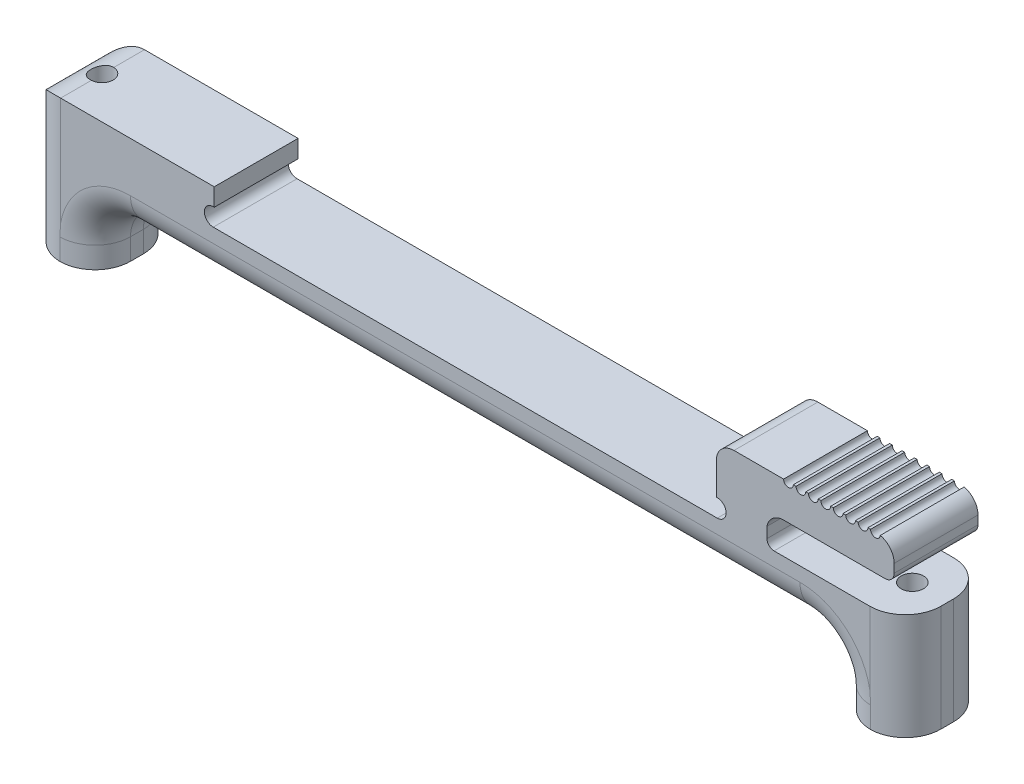
SolidWorks part; units mm, degrees
material "ABS"
ref_plane "Front" through (0, 0, 0) normal (0, 0, 1) x (1, 0, 0)
ref_plane "Top" through (0, 0, 0) normal (0, 1, 0) x (1, 0, 0)
ref_plane "Right" through (0, 0, 0) normal (1, 0, 0) x (0, 0, -1)
ref_axis "Axis1" through (0, 0, 55) along (0, 0, -1)
sketch "Sketch1" plane through (0, 0, 0) normal (0, 0, 1) x (1, 0, 0)
  line L0 (-28.9941, 0) -> (28.9941, 0) construction
  line L1 (-31.4941, 0) -> (-26.4941, 0)
  line L2 (-26.4941, 0) -> (-26.4941, 1.524)
  line L3 (-23.9541, 4.064) -> (23.9541, 4.064)
  line L4 (26.4941, 1.524) -> (26.4941, 0)
  line L5 (26.4941, 0) -> (31.4941, 0)
  line L6 (-31.4941, 0) -> (-31.4941, 10.1561)
  line L7 (-31.4941, 10.1561) -> (-17.9634, 10.1561)
  line L8 (-17.9634, 10.1561) -> (-17.9634, 8.8861)
  line L9 (-18.034, 7.62) -> (18.034, 7.62)
  line L10 (0, 0) -> (0, 15.2653) construction
  line L11 (31.4941, 0) -> (31.4941, 10.1561)
  line L12 (31.4941, 10.1561) -> (17.9634, 10.1561)
  line L13 (17.9634, 10.1561) -> (17.9634, 8.8861)
  arc A0 (-17.9634, 8.8861) -> (-18.034, 7.62) centre (-18.034, 8.255) ccw
  arc A1 (17.9634, 8.8861) -> (18.034, 7.62) centre (18.034, 8.255) cw
  arc A2 (26.4941, 1.524) -> (23.9541, 4.064) centre (23.9541, 1.524) ccw
  arc A3 (-23.9541, 4.064) -> (-26.4941, 1.524) centre (-23.9541, 1.524) ccw
  point P4 (0, 0)
  point P8 (-28.9941, 0)
  point P20 (0, 7.62)
  point P26 (28.9941, 0)
  dimension "D3" = 0.635
  dimension "D9" = 2.54
  dimension "D1" = 57.9882
  dimension "D2" = 5
  dimension "D4" = 36.068
  dimension "D5" = 4.064
  dimension "D6" = 1.27
  dimension "D7" = 13.5307
  dimension "D8" = 3.556
extrude "Boss-Extrude1" add sketch "Sketch1" along normal blind 6
hole_wizard "M2x0.4 Tapped Hole1" positions "Sketch2" profile "Sketch3" tap size "M2x0.4" standard "ANSI Metric" end condition up to next
sketch "Sketch2" plane through (0, 0, 0) normal (0, -1, 0) x (-1, 0, 0)
  line L0 (28.9941, -6) -> (28.9941, 0) construction
  line L1 (31.4941, -6) -> (26.4941, -6) construction
  line L2 (31.4941, 0) -> (26.4941, 0) construction
  line L4 (-28.9941, -6) -> (-28.9941, 0) construction
  line L5 (-26.4941, -6) -> (-31.4941, -6) construction
  line L7 (-26.4941, 0) -> (-31.4941, 0) construction
  point P0 (28.9941, -3)
  point P2 (-28.9941, -3)
sketch "Sketch3" plane through (-28.9941, 0, 3) normal (1, 0, 0) x (0, 0, -1)
  line L0 (0, 0) -> (0, 10.1561)
  line L1 (0, 10.1561) -> (0.8, 10.1561)
  line L2 (0.8, 10.1561) -> (0.8, 0)
  line L5 (0.8, 0) -> (0, 0)
  line L11 (0, -6.35) -> (0, 107.95) construction
  dimension "Thru Tap Drill Dia." = 1.6
  dimension "Thru Tap Drill Depth" = 10.1561
cosmetic thread "Hole Thread1" parameters "D2"=2
cosmetic thread "Hole Thread2" parameters "D2"=2
fillet "Fillet1" radius 2.54 16 edges at (-26.4941, 0.762, 0) (-25.7502, 3.3201, 0) (26.4941, 0.762, 0) (25.7502, 3.3201, 0) (-26.4941, 0.762, 6) (-25.7502, 3.3201, 6) (0, 4.064, 6) (25.7502, 3.3201, 6) (-31.4941, 5.078, 0) (-31.4941, 5.078, 6) (31.4941, 5.078, 0) (31.4941, 5.078, 6) (0, 4.064, 0) (26.4941, 0.762, 6) (31.4941, 10.1561, 3) (-31.4941, 10.1561, 3)
sketch "Sketch4" plane through (0, 0, 6) normal (0, 0, 1) x (1, 0, 0)
  line L0 (28.9541, 10.1561) -> (17.9634, 10.1561) construction
  line L1 (21.59, 10.1561) -> (31.4941, 10.1561)
  line L2 (21.59, 10.1561) -> (21.59, 7.62)
  line L3 (21.59, 7.62) -> (31.4941, 7.62)
  line L4 (31.4941, 10.1561) -> (31.4941, 7.62)
  line L5 (21.59, 10.1561) -> (31.4941, 7.62) construction
  line L6 (21.59, 7.62) -> (31.4941, 10.1561) construction
  line L7 (18.034, 7.62) -> (-18.034, 7.62) construction
  line L8 (31.4941, 7.6161) -> (31.4941, 0) construction
  arc A0 (18.034, 7.62) -> (17.9634, 8.8861) centre (18.034, 8.255) ccw construction
  point P4 (26.542, 8.888)
  dimension "D1" = 3.556
extrude "Cut-Extrude1" cut sketch "Sketch4" against normal through all
sketch "Sketch5" plane through (0, 0, 6) normal (0, 0, 1) x (1, 0, 0)
  line L0 (21.59, 10.1561) -> (21.59, 7.62) construction
  line L1 (22.7817, 9.8735) -> (30.0331, 9.8735)
  line L2 (30.6935, 10.5339) -> (30.6935, 11.1435)
  line L3 (29.0047, 12.4135) -> (28.8134, 12.4135)
  line L4 (17.9634, 11.1435) -> (17.9634, 10.1561)
  line L5 (17.9634, 10.1561) -> (21.59, 10.1561)
  line L6 (21.59, 10.1561) -> (21.59, 8.888)
  line L7 (17.9634, 10.1561) -> (17.9634, 8.8861) construction
  line L11 (22.7817, 12.4135) -> (19.2334, 12.4135)
  line L12 (23.6707, 12.4135) -> (23.4794, 12.4135)
  line L13 (24.5597, 12.4135) -> (24.3684, 12.4135)
  line L14 (25.4487, 12.4135) -> (25.2574, 12.4135)
  line L15 (26.3377, 12.4135) -> (26.1464, 12.4135)
  line L16 (27.2267, 12.4135) -> (27.0354, 12.4135)
  line L17 (28.1157, 12.4135) -> (27.9244, 12.4135)
  arc A0 (21.59, 8.888) -> (22.7817, 9.8735) centre (22.7817, 8.6603) cw
  arc A1 (30.6935, 11.1435) -> (29.701, 12.3829) centre (29.4235, 11.1435) ccw
  arc A2 (19.2334, 12.4135) -> (17.9634, 11.1435) centre (19.2334, 11.1435) ccw
  arc A3 (30.6935, 10.5339) -> (30.0331, 9.8735) centre (30.0331, 10.5339) cw
  arc A4 (22.7817, 12.4135) -> (23.4794, 12.4135) centre (23.1305, 12.4135) ccw
  arc A5 (23.6707, 12.4135) -> (24.3684, 12.4135) centre (24.0195, 12.4135) ccw
  arc A6 (24.5597, 12.4135) -> (25.2574, 12.4135) centre (24.9085, 12.4135) ccw
  arc A7 (25.4487, 12.4135) -> (26.1464, 12.4135) centre (25.7975, 12.4135) ccw
  arc A8 (26.3377, 12.4135) -> (27.0354, 12.4135) centre (26.6865, 12.4135) ccw
  arc A9 (27.2267, 12.4135) -> (27.9244, 12.4135) centre (27.5755, 12.4135) ccw
  arc A10 (28.1157, 12.4135) -> (28.8134, 12.4135) centre (28.4645, 12.4135) ccw
  arc A11 (29.0047, 12.4135) -> (29.701, 12.3829) centre (29.3535, 12.4135) ccw
  point P17 (30.6935, 12.4135)
  point P22 (30.6935, 9.8735)
  dimension "D2" = 1.27
  dimension "D3" = 7.2514
  dimension "D5" = 1.2132
  dimension "D6" = 3.5483
  dimension "D7" = 0.3488
  dimension "D1" = 2.54
  dimension "D8" = 1.5867
  dimension "D9" = 0.6096
  dimension "D4" = 8
extrude "Boss-Extrude2" add sketch "Sketch5" against normal up to surface (6 mm away) up to face at (3.0843, 7.7727, 0)
fillet "Fillet2" radius 0.508 1 edges at (21.59, 7.62, 3)
